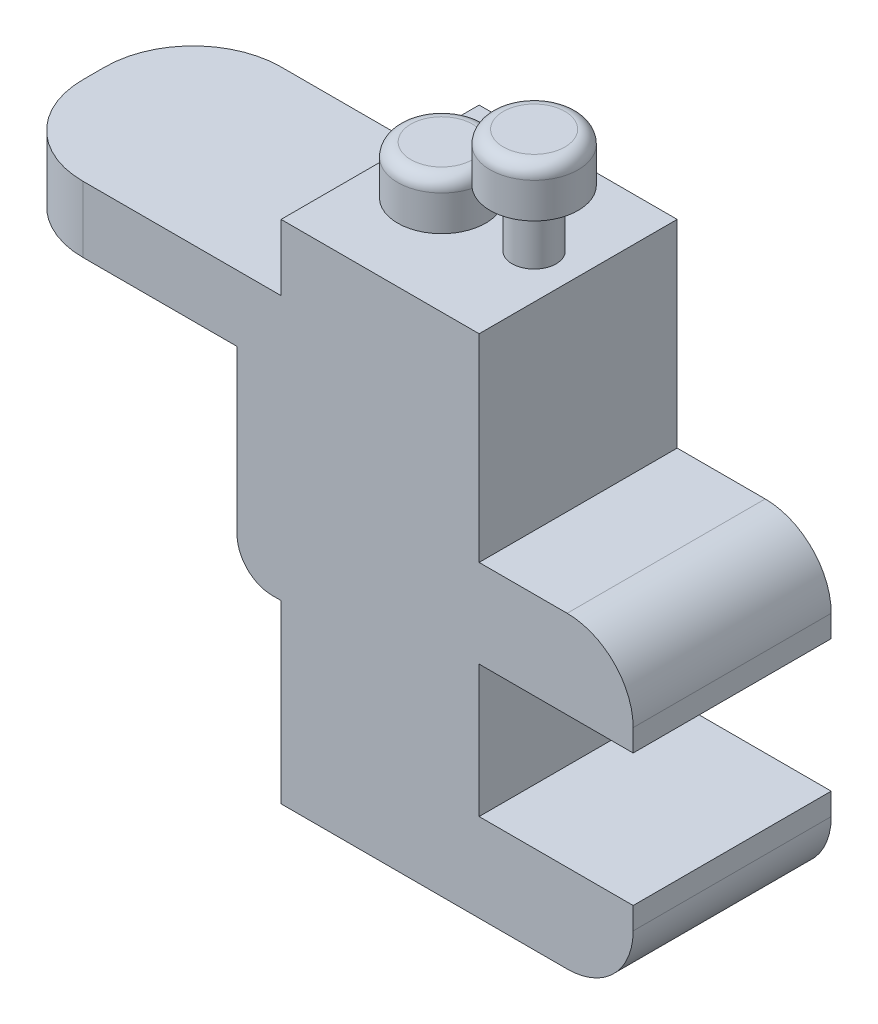
SolidWorks part; units mm, degrees
ref_plane "Front Plane" through (0, 0, 0) normal (0, 0, 1) x (1, 0, 0)
ref_plane "Top Plane" through (0, 0, 0) normal (0, 1, 0) x (1, 0, 0)
ref_plane "Right Plane" through (0, 0, 0) normal (1, 0, 0) x (0, 0, -1)
sketch "Sketch1" plane through (0, 0, 0) normal (0, 0, 1) x (1, 0, 0)
  line L1 (-22.5, -57.5) -> (22.5, -57.5)
  line L2 (-22.5, -57.5) -> (-22.5, 57.5)
  line L3 (-22.5, 57.5) -> (22.5, 57.5)
  line L4 (22.5, -57.5) -> (22.5, 57.5)
  line L5 (-22.5, -57.5) -> (22.5, 57.5) construction
  line L6 (-22.5, 57.5) -> (22.5, -57.5) construction
  point P0 (0, 0)
  dimension "D1" = 115
  dimension "D2" = 45
extrude "Boss-Extrude1" add sketch "Sketch1" against normal blind 45
sketch "Sketch2" plane through (22.5, 0, 0) normal (1, 0, 0) x (0, 0, -1)
  line L0 (45, -57.5) -> (45, 57.5) construction
  line L1 (0, -57.5) -> (45, -57.5)
  line L2 (0, -57.5) -> (0, -37.5)
  line L3 (0, -37.5) -> (45, -37.5)
  line L4 (45, -57.5) -> (45, -37.5)
  line L5 (0, -57.5) -> (0, 57.5) construction
  line L6 (0, -7.5) -> (45, -7.5)
  line L7 (0, -7.5) -> (0, 12.5)
  line L8 (0, 12.5) -> (45, 12.5)
  line L9 (45, -7.5) -> (45, 12.5)
  dimension "D1" = 20
  dimension "D2" = 20
  dimension "D3" = 30
extrude "Boss-Extrude2" add sketch "Sketch2" along normal blind 35
sketch "Sketch3" plane through (0, 0, 0) normal (0, 0, 1) x (1, 0, 0)
  line L0 (-22.5, -17.5) -> (-32.5, -17.5)
  line L1 (-22.5, 57.5) -> (-22.5, -57.5) construction
  line L2 (-22.5, -57.5) -> (57.5, -57.5) construction
  line L3 (-32.5, -17.5) -> (-32.5, 27.5)
  line L4 (-32.5, 27.5) -> (-87.5, 27.5)
  line L5 (-87.5, 27.5) -> (-87.5, 42.5)
  line L6 (-87.5, 42.5) -> (-22.5, 42.5)
  line L7 (-22.5, 42.5) -> (-22.5, -17.5)
  dimension "D1" = 10
  dimension "D2" = 40
  dimension "D3" = 45
  dimension "D4" = 55
  dimension "D5" = 15
extrude "Boss-Extrude3" add sketch "Sketch3" against normal up to surface (45 mm away) up to face at (27.5, -6.5, -45)
sketch "Sketch4" plane through (0, 57.5, 0) normal (0, 1, 0) x (1, 0, 0)
  line L1 (-22.5, 45) -> (-22.5, 0) construction
  line L2 (22.5, 45) -> (22.5, 0) construction
  circle A0 centre (-8.5, 22.5) radius 10
  circle A1 centre (12.5, 22.5) radius 5
  dimension "D1" = 20
  dimension "D2" = 10
  dimension "D3" = 14
  dimension "D4" = 10
extrude "Boss-Extrude4" add sketch "Sketch4" along normal blind 11 contours A0
extrude "Boss-Extrude5" add sketch "Sketch4<3>" along normal blind 13 contours A1
sketch "Sketch4<3>" plane through (0, 57.5, 0) normal (0, 1, 0) x (1, 0, 0) same geometry as "Sketch4"
sketch "Sketch6" plane through (0, 70.5, 0) normal (0, 1, 0) x (1, 0, 0)
  circle A0 centre (12.5, 22.5) radius 10
  dimension "D1" = 20
extrude "Boss-Extrude6" add sketch "Sketch6" along normal blind 11
sketch "Sketch7" plane through (0, 27.5, 0) normal (0, -1, 0) x (1, 0, 0)
  line L0 (-87.5, 0) -> (-32.5, 0) construction
  circle A0 centre (-60, -22.5) radius 10
  point P4 (-60, 0)
  dimension "D1" = 20
  dimension "D2" = 0
extrude "Boss-Extrude7" add sketch "Sketch7" along normal blind 11
fillet "Fillet1" radius 20 2 edges at (-87.5, 35, -45) (-87.5, 35, 0)
fillet "Fillet2" radius 8 1 edges at (-32.5, -17.5, -22.5)
fillet "Fillet3" radius 15 2 edges at (57.5, -57.5, -22.5) (57.5, 12.5, -22.5)
fillet "Fillet4" radius 3 3 edges at (12.5, 81.5, -12.5) (-8.5, 68.5, -12.5) (-50, 16.5, -22.5)
